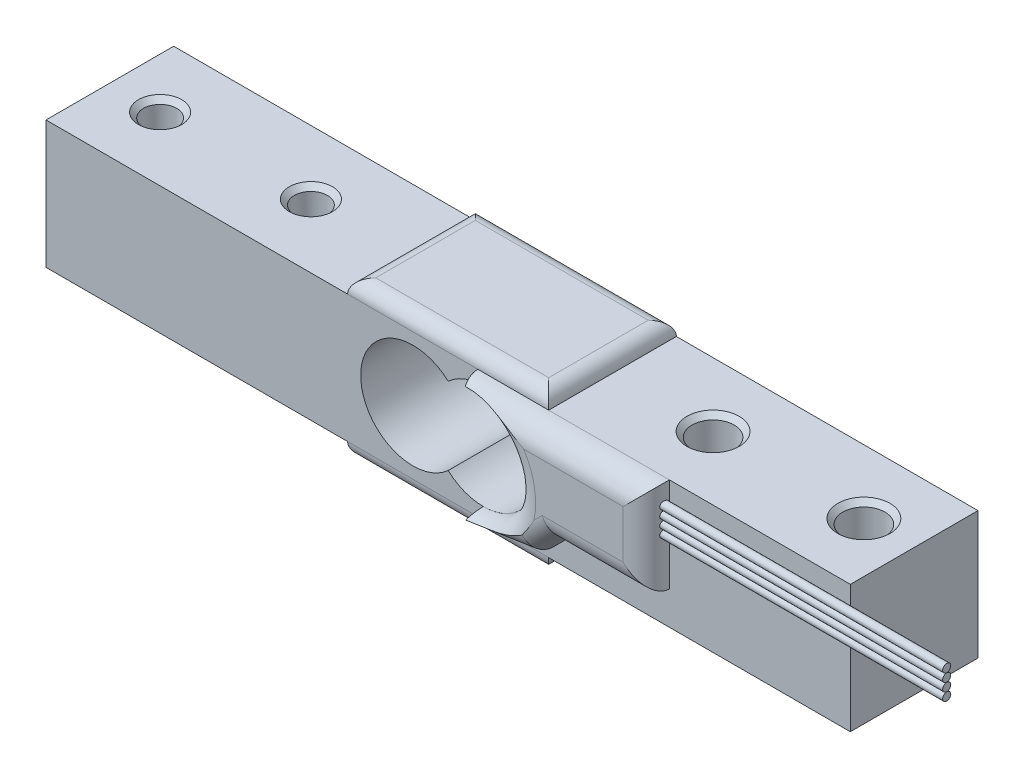
SolidWorks part; units mm, degrees
ref_plane "前视基准面" through (0, 0, 0) normal (0, 0, 1) x (1, 0, 0)
ref_plane "上视基准面" through (0, 0, 0) normal (0, 1, 0) x (1, 0, 0)
ref_plane "右视基准面" through (0, 0, 0) normal (1, 0, 0) x (0, 0, -1)
sketch "草图1" plane through (0, 0, 0) normal (0, 0, 1) x (1, 0, 0)
  line L1 (-40, 6.35) -> (40, 6.35)
  line L2 (-40, 6.35) -> (-40, -6.35)
  line L3 (-40, -6.35) -> (40, -6.35)
  line L4 (40, 6.35) -> (40, -6.35)
  line L5 (-40, 6.35) -> (40, -6.35) construction
  line L6 (-40, -6.35) -> (40, 6.35) construction
  arc A0 (0, 3.8458) -> (0, -3.8458) centre (-3.5, 0) ccw
  arc A2 (0, -3.8458) -> (0, 3.8458) centre (3.5, 0) ccw
  point P0 (0, 0)
  dimension "D1" = 12.7
  dimension "D2" = 80
extrude "凸台-拉伸1" add sketch "草图1" along normal mid plane 12.7
sketch "草图3" plane through (0, 6.35, 0) normal (0, 1, 0) x (1, 0, 0)
  point P0 (-35, 0)
  point P4 (0, 0)
  point P6 (-20, 0)
  point P7 (20, 0)
  point P8 (35, 0)
hole_wizard "M4 螺纹孔1" positions "3D草图1" profile "草图4" tap size "M4" standard "GB" end condition through all
sketch3d "3D草图1"
  point P0 (-35, 6.35, 0)
  point P3 (-20, 6.35, 0)
sketch "草图4" plane through (-35, 6.35, 0) normal (1, 0, 0) x (0, 0, 1)
  line L0 (0, 0) -> (0, 12.7)
  line L1 (0, 12.7) -> (1.65, 12.7)
  line L2 (1.65, 12.7) -> (1.65, 0)
  line L5 (1.65, 0) -> (0, 0)
  line L11 (0, -6.35) -> (0, 107.95) construction
  dimension "通孔螺纹孔钻头直径" = 3.3
  dimension "通孔螺纹孔钻头深度" = 12.7
cosmetic thread "孔螺蚊线1" parameters "D2"=4
cosmetic thread "孔螺蚊线2" parameters "D2"=4
hole_wizard "M5 螺纹孔1" positions "3D草图2" profile "草图5" tap size "M5" standard "GB" end condition through all
sketch3d "3D草图2"
  point P0 (20, 6.35, 0)
  point P3 (35, 6.35, 0)
sketch "草图5" plane through (20, 6.35, 0) normal (1, 0, 0) x (0, 0, 1)
  line L0 (0, 0) -> (0, 12.7)
  line L1 (0, 12.7) -> (2.1, 12.7)
  line L2 (2.1, 12.7) -> (2.1, 0)
  line L5 (2.1, 0) -> (0, 0)
  line L11 (0, -6.35) -> (0, 107.95) construction
  dimension "通孔螺纹孔钻头直径" = 4.2
  dimension "通孔螺纹孔钻头深度" = 12.7
cosmetic thread "孔螺蚊线3" parameters "D2"=5
cosmetic thread "孔螺蚊线4" parameters "D2"=5
chamfer "倒角1" distance 0.5 angle 45 8 edges at (-35, -6.35, 1.65) (-20, -6.35, 1.65) (35, -6.35, 2.1) (20, -6.35, 2.1) (35, 6.35, 2.1) (20, 6.35, 2.1) (-20, 6.35, 1.65) (-35, 6.35, 1.65)
sketch "草图2" plane through (0, 0, 0) normal (0, 0, 1) x (1, 0, 0)
  line L0 (40, 6.35) -> (-40, 6.35) construction
  line L1 (-10, 7.75) -> (10, 7.75)
  line L2 (-10, 7.75) -> (-10, 6.35)
  line L3 (-10, -7.75) -> (10, -7.75)
  line L4 (10, 7.75) -> (10, 6.35)
  line L5 (-10, 7.75) -> (-8.1935, 6.35) construction
  line L6 (-10, -7.75) -> (-8.1935, -6.35) construction
  line L7 (-10, 6.35) -> (10, 6.35)
  line L9 (-10, -6.35) -> (10, -6.35)
  line L13 (-10, -6.35) -> (-10, -7.75)
  line L14 (8.1935, -6.35) -> (10, -7.75) construction
  line L15 (8.1935, 6.35) -> (10, 7.75) construction
  line L17 (10, -6.35) -> (10, -7.75)
  point P0 (0, 0)
  point P5 (0, 0)
  dimension "D1" = 0
  dimension "D2" = 20
  dimension "D3" = 1.4
extrude "凸台-拉伸2" add sketch "草图2" along normal mid plane 12.7 separate body
fillet "圆角1" radius 1.4 4 edges at (10, 7.75, 0) (0, 7.75, 6.35) (-10, 7.75, 0) (0, 7.75, -6.35)
fillet "圆角2" radius 1.4 4 edges at (-10, -7.75, 0) (0, -7.75, 6.35) (10, -7.75, 0) (0, -7.75, -6.35)
sketch "草图6" plane through (0, 0, 6.35) normal (0, 0, 1) x (1, 0, 0)
  line L0 (3.5, 5.2) -> (2.947, 6.35)
  line L1 (-10, 6.35) -> (10, 6.35) construction
  line L2 (3.5, -5.2) -> (2.947, -6.35)
  line L3 (10, -6.35) -> (-10, -6.35) construction
  line L4 (2.947, 6.35) -> (22, 6.35)
  line L5 (22, 6.35) -> (22, -3.05)
  line L6 (22, -3.05) -> (12.6, -3.05)
  line L7 (12.6, -3.05) -> (10.45, -5.2)
  line L8 (10.45, -5.2) -> (2.947, -6.35)
  arc A0 (3.5, -5.2) -> (3.5, 5.2) centre (3.5, 0) ccw
extrude "凸台-拉伸3" add sketch "草图6" along normal blind 2.3 separate body
fillet "圆角3" radius 2.3 6 edges at (12.4735, 6.35, 8.65) (22, 1.65, 8.65) (17.3, -3.05, 8.65) (11.525, -4.125, 8.65) (8.7, 0, 8.65) (6.6985, -5.775, 8.65)
ref_plane "基准面1" through (20, 0, 0) normal (1, 0, 0) x (0, 0, -1)
sketch "草图7" plane through (20, 0, 0) normal (1, 0, 0) x (0, 0, -1)
  circle A0 centre (-6.76, 4.35) radius 0.4
  circle A1 centre (-6.76, 3.53) radius 0.4
  circle A2 centre (-6.76, 2.71) radius 0.4
  circle A3 centre (-6.76, 1.89) radius 0.4
extrude "凸台-拉伸4" add sketch "草图7" along normal blind 30
sketch "草图8" plane through (0, 0, 6.35) normal (0, 0, 1) x (1, 0, 0)
  line L0 (1386.854, 682.1925) -> (2694.1873, 682.1925) construction
  line L1 (83.0964, 242.9588) -> (557.0964, 242.9588) construction
